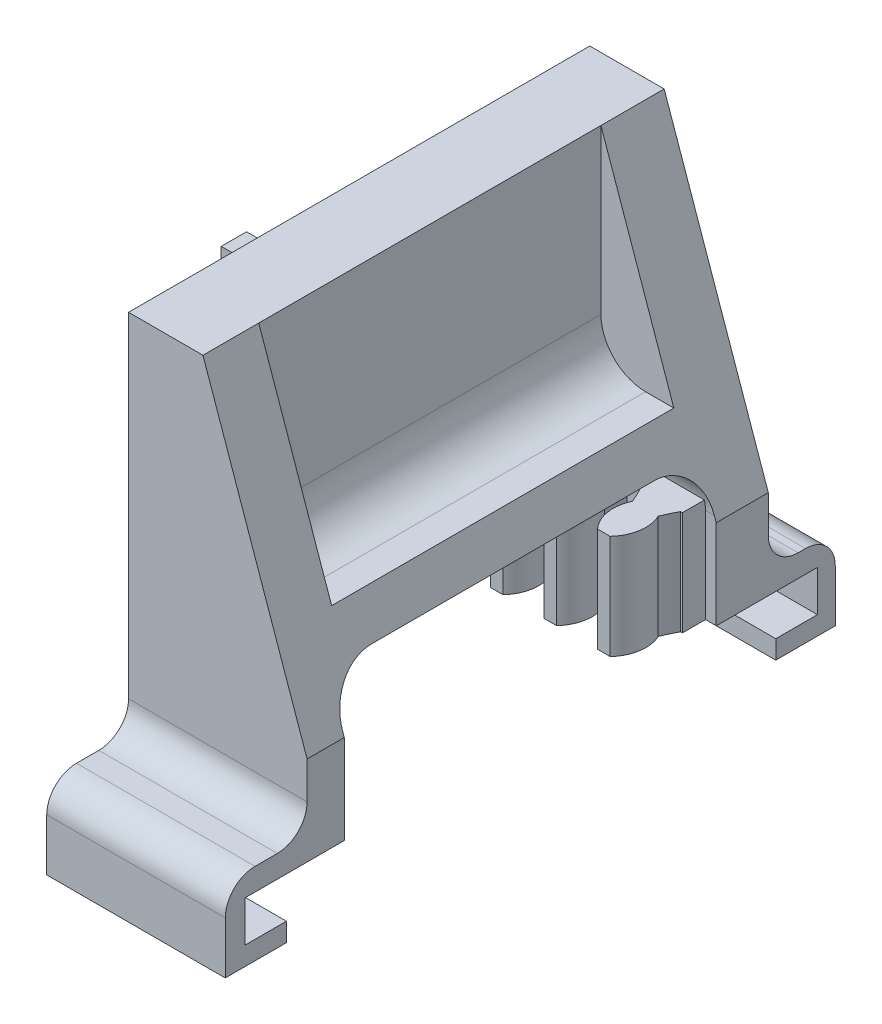
SolidWorks part; units mm, degrees
ref_plane "Front Plane" through (0, 0, 0) normal (0, 0, 1) x (1, 0, 0)
ref_plane "Top Plane" through (0, 0, 0) normal (0, 1, 0) x (1, 0, 0)
ref_plane "Right Plane" through (0, 0, 0) normal (1, 0, 0) x (0, 0, -1)
sketch "Sketch1" plane through (0, 0, 0) normal (0, 0, 1) x (1, 0, 0)
  line L0 (0, 0) -> (0, -30)
  line L1 (0, -30) -> (12, -30)
  line L2 (12, -30) -> (12, -20)
  line L3 (12, -20) -> (5, 0)
  line L4 (5, 0) -> (0, 0)
  dimension "D1" = 30
  dimension "D2" = 12
  dimension "D3" = 10
  dimension "D4" = 5
extrude "Boss-Extrude1" add sketch "Sketch1" against normal blind 31
sketch "Sketch4" plane through (0, 0, 0) normal (-1, 0, 0) x (0, 0, 1)
  line L0 (-31, 0) -> (-31, -30) construction
  line L1 (-27.5, -16.6434) -> (-2.5, -16.6434)
  line L2 (-27.5, -16.6434) -> (-27.5, -31.6434)
  line L3 (-27.5, -31.6434) -> (-2.5, -31.6434)
  line L4 (-2.5, -16.6434) -> (-2.5, -31.6434)
  point P4 (-27.5, -24.1434)
  dimension "D1" = 25
  dimension "D2" = 15
  dimension "D3" = 3.5
extrude "Cut-Extrude2" cut sketch "Sketch4" against normal blind 25 contours L2 L1 L4 L3
ref_plane "Plane1" through (0, 0, -15.25) normal (0, 0, 1) x (1, 0, 0)
sketch "Sketch6" plane through (0, 0, -15.25) normal (0, 0, 1) x (1, 0, 0)
  line L0 (5, 0) -> (5, -14)
  line L1 (5, -14) -> (9.9, -14)
  line L2 (12, -20) -> (5, 0) construction
  line L3 (9.9, -14) -> (5, 0)
  dimension "D1" = 14
extrude "Cut-Extrude4" cut sketch "Sketch6" against normal mid plane 23
ref_plane "Plane3" through (0, -26, 0) normal (0, 1, 0) x (1, 0, 0)
sketch "Sketch7" plane through (0, -26, 0) normal (0, 1, 0) x (1, 0, 0)
  line L0 (11.2768, 27.65) -> (-19.7232, 27.65)
  line L62 (-16.5, 15.25) -> (16.5, 15.25) construction
  line L162 (11.2768, 27.65) -> (11.2768, 25.95)
  line L172 (-19.7232, 25.95) -> (-19.7232, 27.65)
  line L243 (11.2768, 25.95) -> (-19.7232, 25.95)
  dimension "D2" = 31
  dimension "D3" = 1.7
  dimension "D7" = 12.4
extrude "Boss-Extrude3" add sketch "Sketch7" along normal blind 7
sketch "Sketch10" plane through (0, -26, 0) normal (0, 1, 0) x (1, 0, 0)
  line L1 (9.8022, 22.1441) -> (9.8022, 23.4692) construction
  line L2 (10.2262, 22.1441) -> (9.3781, 22.1441)
  line L4 (-19.7232, 25.95) -> (11.2768, 25.95) construction
  line L5 (8.4522, 25.95) -> (11.1522, 25.95)
  arc A0 (10.2262, 22.1441) -> (10.6705, 24.929) centre (8.3868, 23.8654) ccw
  arc A1 (10.6705, 24.929) -> (11.1522, 25.95) centre (19.5896, 21.3459) cw
  arc A2 (8.9338, 24.929) -> (8.4522, 25.95) centre (0.0147, 21.3459) ccw
  arc A3 (9.3781, 22.1441) -> (8.9338, 24.929) centre (11.2175, 23.8654) cw
  dimension "D1" = 2.7
extrude "Boss-Extrude4" add sketch "Sketch10" along normal blind 7
pattern_linear "LPattern1" count 8 spacing 3.6 along (-1, 0, 0) of "Boss-Extrude4"
sketch "Sketch11" plane through (0, 0, -31) normal (0, 0, -1) x (-1, 0, 0)
  line L0 (-12, -30) -> (-12, -20) construction
  line L1 (-12, -24.5) -> (0, -24.5)
  line L2 (-12, -24.5) -> (-12, -30)
  line L3 (-12, -30) -> (0, -30)
  line L4 (0, -24.5) -> (0, -30)
  dimension "D1" = 5.5
extrude "Boss-Extrude5" add sketch "Sketch11" along normal blind 4.5
fillet "Fillet5" radius 3 3 edges at (5, -14, -15.25) (5.4126, -16.6434, -2.5) (5.4126, -16.6434, -27.5)
sketch "Sketch12" plane through (0, 0, 0) normal (0, 0, 1) x (1, 0, 0)
  line L0 (12, -30) -> (12, -20) construction
  line L1 (0, -30) -> (12, -30)
  line L2 (0, -30) -> (0, -24.5)
  line L3 (0, -24.5) -> (12, -24.5)
  line L4 (12, -30) -> (12, -24.5)
  dimension "D1" = 5.5
extrude "Boss-Extrude6" add sketch "Sketch12" along normal blind 5.5
sketch "Sketch13" plane through (0, 0, 0) normal (-1, 0, 0) x (0, 0, 1)
  line L0 (-34.3, -26) -> (-27.5, -26)
  line L1 (-27.5, -26) -> (-27.5, -32.0691)
  line L2 (-27.5, -32.0691) -> (-31.5, -32.0691)
  line L3 (-31.5, -32.0691) -> (-31.5, -28.75)
  line L4 (-31.5, -28.75) -> (-34.3, -28.75)
  line L5 (-34.3, -28.75) -> (-34.3, -26)
  line L6 (-15.0561, -22.9316) -> (-15.0561, -37.9805) construction
  line L7 (-2.5, -30) -> (5.5, -30) construction
  line L9 (-27.5, -26) -> (-27.5, -30) construction
  line L12 (1.3878, -28.75) -> (4.1878, -28.75)
  line L13 (1.3878, -32.0691) -> (1.3878, -28.75)
  line L14 (-2.6122, -32.0691) -> (1.3878, -32.0691)
  line L15 (-2.6122, -26) -> (-2.6122, -32.0691)
  line L16 (4.1878, -26) -> (-2.6122, -26)
  line L17 (4.1878, -28.75) -> (4.1878, -26)
  dimension "D1" = 6.8
  dimension "D2" = 0
  dimension "D3" = 4
  dimension "D4" = 2.75
  dimension "D5" = 4
extrude "Cut-Extrude5" cut sketch "Sketch13" against normal up to surface (12 mm away) up to face at (12, -24.8333, 1)
fillet "Fillet6" radius 2 4 edges at (6, -24.5, -35.5) (6, -24.5, -31) (6, -24.5, 5.5) (6, -24.5, 0)
